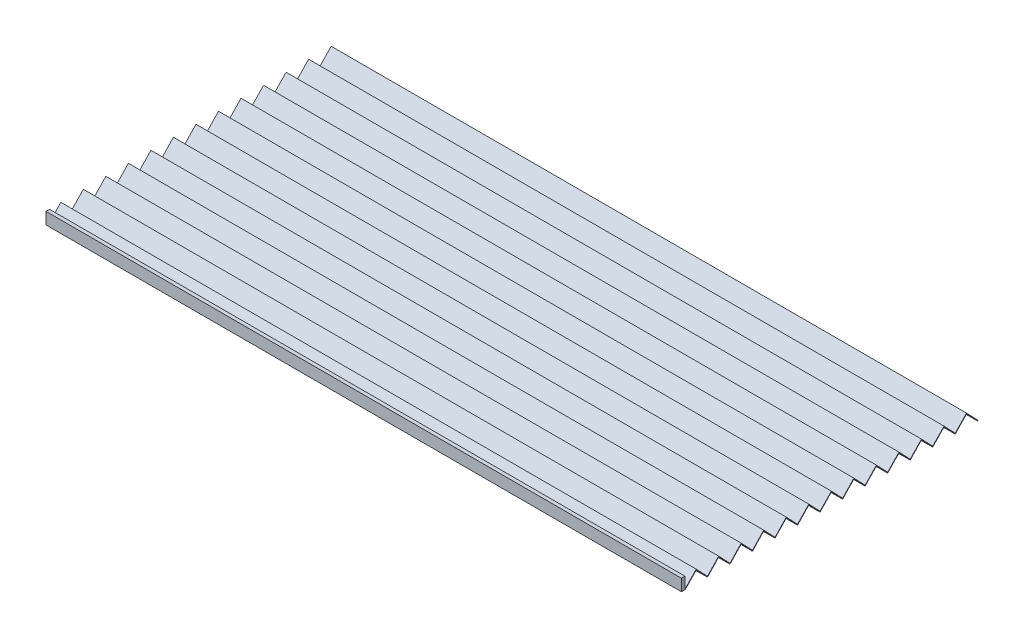
SolidWorks part; units mm, degrees
ref_plane "Front Plane" through (0, 0, 0) normal (0, 0, 1) x (1, 0, 0)
ref_plane "Top Plane" through (0, 0, 0) normal (0, 1, 0) x (1, 0, 0)
ref_plane "Right Plane" through (0, 0, 0) normal (1, 0, 0) x (0, 0, -1)
sketch "Sketch2" plane through (0, 0, 0) normal (0, 0, 1) x (1, 0, 0)
  line L1 (-270, 10) -> (270, 10)
  line L2 (-270, 10) -> (-270, 0)
  line L3 (-270, 0) -> (270, 0)
  line L4 (270, 10) -> (270, 0)
  point P4 (0, 0)
  dimension "D1" = 10
  dimension "D2" = 540
extrude "Boss-Extrude1" add sketch "Sketch2" along normal blind 3
sketch "Sketch3" plane through (270, 0, 0) normal (1, 0, 0) x (0, 0, -1)
  line L0 (0, 10) -> (248.9046, 10) construction
  line L1 (0, 0) -> (248.9046, 0) construction
  line L3 (0, 0) -> (9.5733, 10)
  line L4 (9.5733, 10) -> (19.1465, 0)
  line L5 (19.1465, 0) -> (28.7198, 10)
  line L6 (28.7198, 10) -> (38.293, 0)
  line L7 (38.293, 0) -> (47.8663, 10)
  line L8 (47.8663, 10) -> (57.4395, 0)
  line L9 (57.4395, 0) -> (67.0128, 10)
  line L10 (67.0128, 10) -> (76.586, 0)
  line L11 (76.586, 0) -> (86.1593, 10)
  line L12 (86.1593, 10) -> (95.7325, 0)
  line L13 (95.7325, 0) -> (105.3058, 10)
  line L14 (105.3058, 10) -> (114.879, 0)
  line L15 (114.879, 0) -> (124.4523, 10)
  line L16 (124.4523, 10) -> (134.0255, 0)
  line L17 (134.0255, 0) -> (143.5988, 10)
  line L18 (143.5988, 10) -> (153.172, 0)
  line L20 (153.172, 0) -> (162.7453, 10)
  line L21 (162.7453, 10) -> (172.3185, 0)
  line L22 (172.3185, 0) -> (181.8918, 10)
  line L23 (181.8918, 10) -> (191.465, 0)
  line L24 (191.465, 0) -> (201.0383, 10)
  line L25 (201.0383, 10) -> (210.6115, 0)
  line L26 (210.6115, 0) -> (220.1848, 10)
  line L27 (220.1848, 10) -> (229.758, 0)
  line L28 (229.758, 0) -> (239.3313, 10)
  line L29 (239.3313, 10) -> (248.9046, 0)
  line L30 (248.9046, 10) -> (248.9046, 0) construction
  line L32 (248.9046, 10) -> (248.9046, 0) construction
extrude "Extrude-Thin1" add sketch "Sketch3" against normal through all thin thin type mid plane wall 0.5
